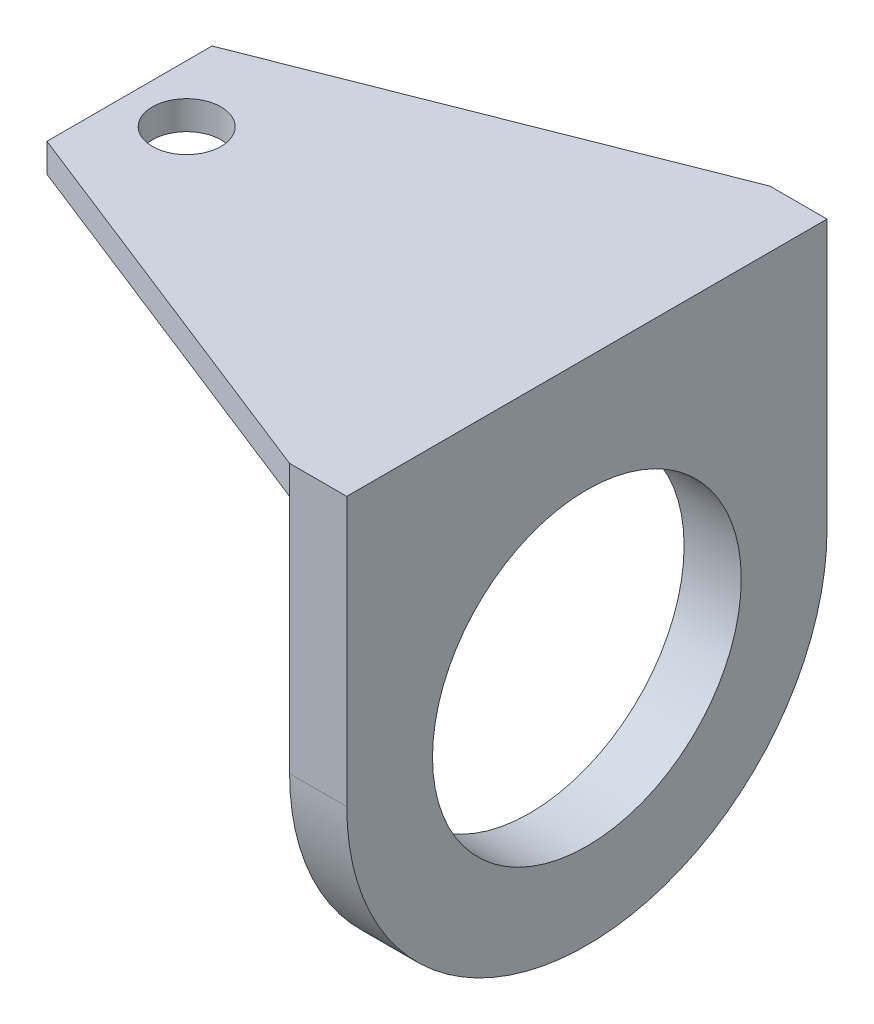
SolidWorks part; units mm, degrees
ref_plane "Front Plane" through (0, 0, 0) normal (0, 0, 1) x (1, 0, 0)
ref_plane "Top Plane" through (0, 0, 0) normal (0, 1, 0) x (1, 0, 0)
ref_plane "Right Plane" through (0, 0, 0) normal (1, 0, 0) x (0, 0, -1)
sketch "Sketch1" plane through (0, 0, 0) normal (1, 0, 0) x (0, 0, -1)
  circle A0 centre (0, 0) radius 13.5
  circle A1 centre (0, 0) radius 21
  dimension "D1" = 27
  dimension "D2" = 7.5
extrude "Boss-Extrude1" add sketch "Sketch1" along normal blind 5
ref_plane "Plane1" through (0, 21, 0) normal (0, 1, 0) x (1, 0, 0)
sketch "Sketch2" plane through (0, 21, 0) normal (0, 1, 0) x (1, 0, 0)
  line L0 (5, -21) -> (5, 21) construction
  line L1 (5, -21) -> (5, 21)
  line L2 (0, 21) -> (0, -21) construction
  line L3 (0, 21) -> (0, -21)
  line L4 (5, -21) -> (-35, -21)
  line L5 (-35, -21) -> (-35, 21)
  line L6 (-35, 21) -> (5, 21)
  line L7 (-30, 0) -> (-42.2528, 0) construction
  circle A1 centre (-30, 0) radius 3
  dimension "D2" = 6
  dimension "D4" = 2
  dimension "D1" = 40
extrude "Boss-Extrude2" add sketch "Sketch2" against normal up to surface (21 mm away) contours L6 L3 L4 L1 region at (2.5, 21, 0) up to face at (5, 0, -21)
extrude "Boss-Extrude3" add sketch "Sketch2<3>" along normal blind 2.5 contours L6 L5 L4 L3 | L6 L3 L4 L1 | A1 L5 L4 | A1 L6 L5 | L6 | L4 region at (2.5, 21, 0) region at (-17.2549, 21, 0)
sketch "Sketch2<3>" plane through (0, 21, 0) normal (0, 1, 0) x (1, 0, 0) same geometry as "Sketch2"
ref_point "Point1"
sketch "Sketch3" plane through (0, 21, 0) normal (0, -1, 0) x (1, 0, 0)
  line L0 (0, -21) -> (-35, -7.216)
  line L1 (-35, 21) -> (-35, -21) construction
  line L2 (-35, -7.216) -> (-35, 7.216)
  line L3 (-30, 0) -> (-42.2327, 0) construction
  line L4 (0, -21) -> (0, 21) construction
  line L5 (0, -21) -> (0, 21)
  line L6 (0, 21) -> (-35, 7.216)
  line L7 (0, -21) -> (0, -28.4718)
  line L8 (0, -28.4718) -> (-40.7638, -28.4718)
  line L9 (-40.7638, -28.4718) -> (-40.7638, 27.2513)
  line L10 (-40.7638, 27.2513) -> (0, 27.2513)
  line L11 (0, 27.2513) -> (0, 21)
  point P12 (-35, 0)
  line M7 (-35, -21) -> (0, -21)
  line M9 (0, 21) -> (-35, 21)
  line M10 (-35, 21) -> (-35, -21)
extrude "Cut-Extrude4" cut sketch "Sketch3" against normal through all contours L2 L3 L9 L8 L7 M7 M10 | L3 L11 L10 L9 M10 M9 | L0 M7 M10 | L6 M9 M10 region at (-23.3333, 21, -16.4053) region at (-0.4972, 21, -24.7359) region at (-17.5, 21, 21.4903) region at (-23.3333, 21, 16.4053)
